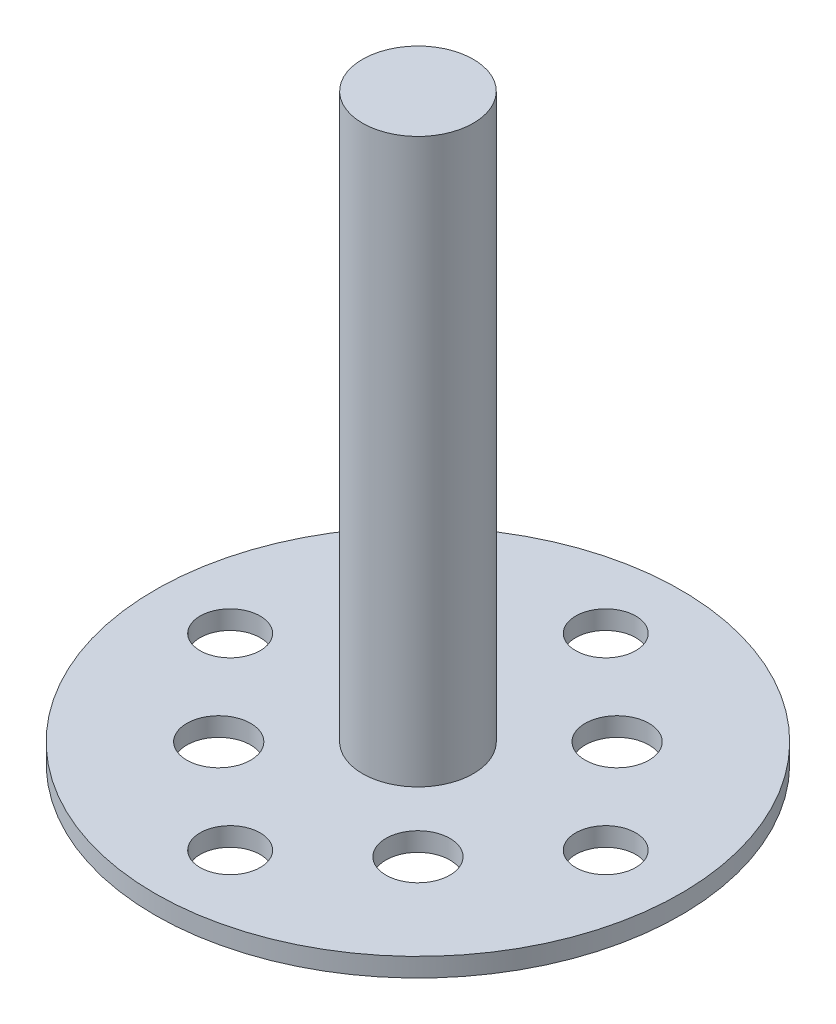
SolidWorks part; units mm, degrees
ref_plane "Front Plane" through (0, 0, 0) normal (0, 0, 1) x (1, 0, 0)
ref_plane "Top Plane" through (0, 0, 0) normal (0, 1, 0) x (1, 0, 0)
ref_plane "Right Plane" through (0, 0, 0) normal (1, 0, 0) x (0, 0, -1)
sketch "Sketch1" plane through (0, 0, 0) normal (0, 1, 0) x (1, 0, 0)
  line L0 (-5.3033, 5.3033) -> (0, 0) construction
  line L1 (0, 0) -> (-5.3033, -5.3033) construction
  line L2 (0, -55) -> (0, 55) construction
  line L3 (5.3033, 5.3033) -> (0, 0) construction
  line L4 (0, 0) -> (5.3033, -5.3033) construction
  circle A0 centre (0, 0) radius 14
  circle A1 centre (0, 0) radius 10
  circle A2 centre (0, 10) radius 1.6
  circle A3 centre (10, 0) radius 1.6
  circle A4 centre (0, -10) radius 1.6
  circle A5 centre (-10, 0) radius 1.6
  circle A6 centre (-5.3033, 5.3033) radius 1.7
  circle A7 centre (-5.3033, -5.3033) radius 1.7
  circle A8 centre (5.3033, 5.3033) radius 1.7
  circle A9 centre (5.3033, -5.3033) radius 1.7
  circle A10 centre (0, 0) radius 2.95
  circle A11 centre (0, 0) radius 7.5 construction
  point P15 (0, 0)
  dimension "D1" = 28
  dimension "D2" = 20
  dimension "D3" = 3.2
  dimension "D4" = 4
  dimension "D5" = 5.9
  dimension "D6" = 15
  dimension "D7" = 3.4
  dimension "D8" = 3.4
extrude "Boss-Extrude1" add sketch "Sketch1" along normal blind 1 contours A0 A5 A1 A2 A3 A4 | A5 A1 A4 A3 A2 A10 A8 A7 A6 A9 region at (-13.604, 0, 0) region at (8.1208, 0, 0)
extrude "Boss-Extrude2" add sketch "Sketch1<3>" along normal blind 31 contours A10 region at (0, 0, 0)
sketch "Sketch1<3>" plane through (0, 0, 0) normal (0, 1, 0) x (1, 0, 0) same geometry as "Sketch1"
